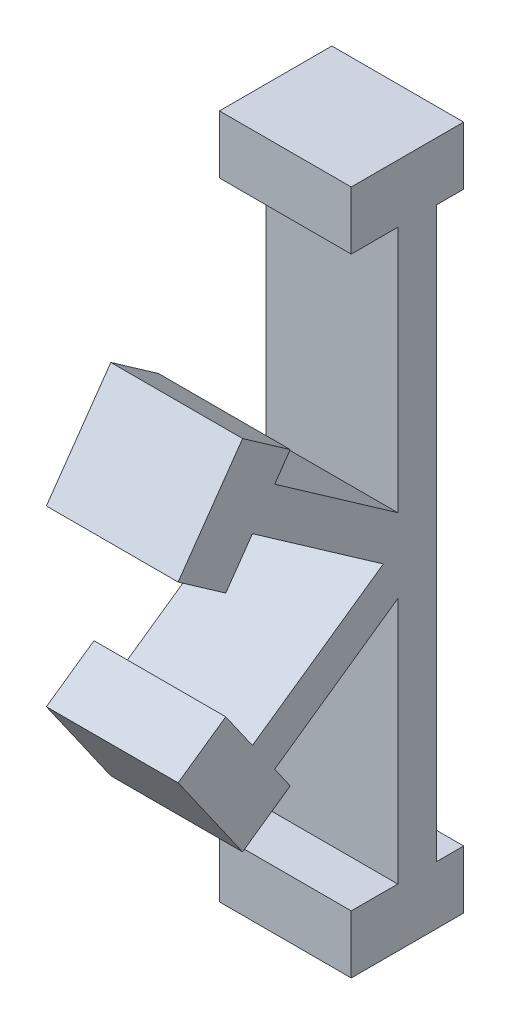
SolidWorks part; units mm, degrees
ref_plane "Front Plane" through (0, 0, 0) normal (0, 0, 1) x (1, 0, 0)
ref_plane "Top Plane" through (0, 0, 0) normal (0, 1, 0) x (1, 0, 0)
ref_plane "Right Plane" through (0, 0, 0) normal (1, 0, 0) x (0, 0, -1)
sketch "Sketch2" plane through (0, 0, 0) normal (0, 0, 1) x (1, 0, 0)
  line L1 (-73.75, 88.375) -> (73.75, 88.375)
  line L2 (-73.75, 88.375) -> (-73.75, -88.375)
  line L3 (-73.75, -88.375) -> (73.75, -88.375)
  line L4 (73.75, 88.375) -> (73.75, -88.375)
  line L5 (-73.75, 88.375) -> (73.75, -88.375) construction
  line L6 (-73.75, -88.375) -> (73.75, 88.375) construction
  point P0 (0, 0)
  dimension "D1" = 147.5
  dimension "D2" = 176.75
extrude "Boss-Extrude1" add sketch "Sketch2" along normal blind 10
sketch "Sketch3" plane through (-73.75, 0, 0) normal (-1, 0, 0) x (0, 0, 1)
  line L0 (0, 88.375) -> (0, -88.375) construction
  line L1 (-7, 88.375) -> (22, 88.375)
  line L2 (-7, 88.375) -> (-7, 73.375)
  line L3 (-7, 73.375) -> (22, 73.375)
  line L4 (22, 88.375) -> (22, 73.375)
  line L5 (10, 88.375) -> (10, -88.375) construction
  line L6 (0, 0) -> (56.8374, 0) construction
  line L7 (22, -88.375) -> (22, -73.375)
  line L8 (-7, -88.375) -> (-7, -73.375)
  line L9 (-7, -88.375) -> (22, -88.375)
  line L10 (-7, -73.375) -> (22, -73.375)
  line L11 (10, 88.375) -> (0, 88.375) construction
  dimension "D1" = 7
  dimension "D2" = 12
  dimension "D3" = 15
  dimension "D4" = 0
extrude "Boss-Extrude2" add sketch "Sketch3" against normal blind 34
ref_plane "Plane1" through (0, 0, 0) normal (1, 0, 0) x (0, 0, -1)
mirror "Mirror1" about plane through (0, 0, 0) normal (1, 0, 0) of "Boss-Extrude2"
sketch "Sketch5" plane through (-73.75, 0, 0) normal (-1, 0, 0) x (0, 0, 1)
  line L0 (10, 73.375) -> (10, -73.375) construction
  line L1 (-35, 0) -> (-35, 43.6802) construction
  line L2 (0, 0) -> (0, 73.375) construction
  line L3 (0, 0) -> (10, 0)
  line L4 (-35, 0) -> (0, 0) construction
  line L5 (-7, 88.375) -> (22, 88.375)
  line L6 (-7, 88.375) -> (-7, 73.375)
  line L7 (-7, 73.375) -> (22, 73.375)
  line L8 (22, 88.375) -> (22, 73.375)
  line L9 (0, 73.375) -> (10, 73.375)
  line L10 (0, 73.375) -> (0, 0)
  line L11 (0, 0) -> (10, 0)
  line L12 (10, 73.375) -> (10, 0)
  line L13 (5, 0) -> (5, -4.9122)
  line L18 (58.2224, 51.916) -> (50.0308, 46.1802)
  line L19 (-7, 73.375) -> (22, 73.375)
  line L20 (-7, 73.375) -> (-7, 63.375)
  line L21 (-7, 63.375) -> (22, 63.375)
  line L22 (22, 73.375) -> (22, 63.375)
  line L23 (50.0308, 46.1802) -> (66.6646, 22.4248)
  line L24 (58.2224, 51.916) -> (74.8561, 28.1606)
  line L25 (74.8561, 28.1606) -> (66.6646, 22.4248)
  line L26 (67.9732, 37.9904) -> (7.8679, -4.0958)
  line L27 (62.2374, 46.1819) -> (2.1321, 4.0958)
  line L28 (2.1321, 4.0958) -> (7.8679, -4.0958)
  line L29 (2.1321, -4.0958) -> (7.8679, 4.0958)
  line L30 (62.2374, -46.1819) -> (2.1321, -4.0958)
  line L31 (67.9732, -37.9904) -> (7.8679, 4.0958)
  line L32 (5, 0) -> (5, 4.9122)
  line L33 (74.8561, -28.1606) -> (66.6646, -22.4248)
  line L34 (58.2224, -51.916) -> (74.8561, -28.1606)
  line L35 (50.0308, -46.1802) -> (66.6646, -22.4248)
  line L36 (58.2224, -51.916) -> (50.0308, -46.1802)
  line L37 (50.0308, 46.1802) -> (66.6646, 22.4248)
  line L38 (-7, 63.375) -> (22, 63.375)
  line L39 (-7, 63.375) -> (-7, 48.375)
  line L40 (-7, 48.375) -> (22, 48.375)
  line L41 (22, 63.375) -> (22, 48.375)
  line L42 (50.0308, 46.1802) -> (37.7436, 37.5766)
  line L43 (37.7436, 37.5766) -> (54.3773, 13.8212)
  line L44 (66.6646, 22.4248) -> (54.3773, 13.8212)
  line L45 (50.0308, -46.1802) -> (66.6646, -22.4248)
  line L46 (66.6646, -22.4248) -> (54.3773, -13.8212)
  line L47 (50.0308, -46.1802) -> (37.7436, -37.5766)
  line L48 (37.7436, -37.5766) -> (54.3773, -13.8212)
  circle A0 centre (-35, 0) radius 110
  point P17 (-35, 0)
  point P31 (5, 0)
  point P34 (5, 0)
  point P51 (5, 0)
  line M9 (10, -73.375) -> (10, 73.375)
  dimension "D3" = 10
  dimension "D1" = 220
  dimension "D2" = 35
  dimension "D5" = 15
  dimension "D4" = 2
  dimension "D6" = 2
extrude "Boss-Extrude3" add sketch "Sketch5" against normal blind 34 contours L31 L26 L23 L27 L12 | L30 L35 L31 L26 M9 | L26 L31 M9 | L44 L23 L26 L43 | L27 L43 L26 L23 | L42 L43 L27 L23 | L48 L47 L35 L30 | L48 L30 L35 L31 | L48 L31 L35 L46 region at (-73.75, 0, 11.2391) region at (-73.75, 15.8458, 27.7303) region at (-73.75, -15.8458, 27.7303) region at (-73.75, 39.0114, 45.8947) region at (-73.75, 32.0486, 50.7701) region at (-73.75, -32.0486, 50.7701) region at (-73.75, -39.0114, 45.8947) region at (-73.75, 23.0379, 57.0795) region at (-73.75, -23.0379, 57.0795)
sketch "Sketch8" plane through (0, 0, 22) normal (0, 0, 1) x (1, 0, 0)
  line L1 (73.75, 88.375) -> (-39.75, 88.375)
  line L2 (73.75, 88.375) -> (73.75, -88.375)
  line L3 (73.75, -88.375) -> (-39.75, -88.375)
  line L4 (-39.75, 88.375) -> (-39.75, -88.375)
extrude "Cut-Extrude1" cut sketch "Sketch8" against normal blind 30
